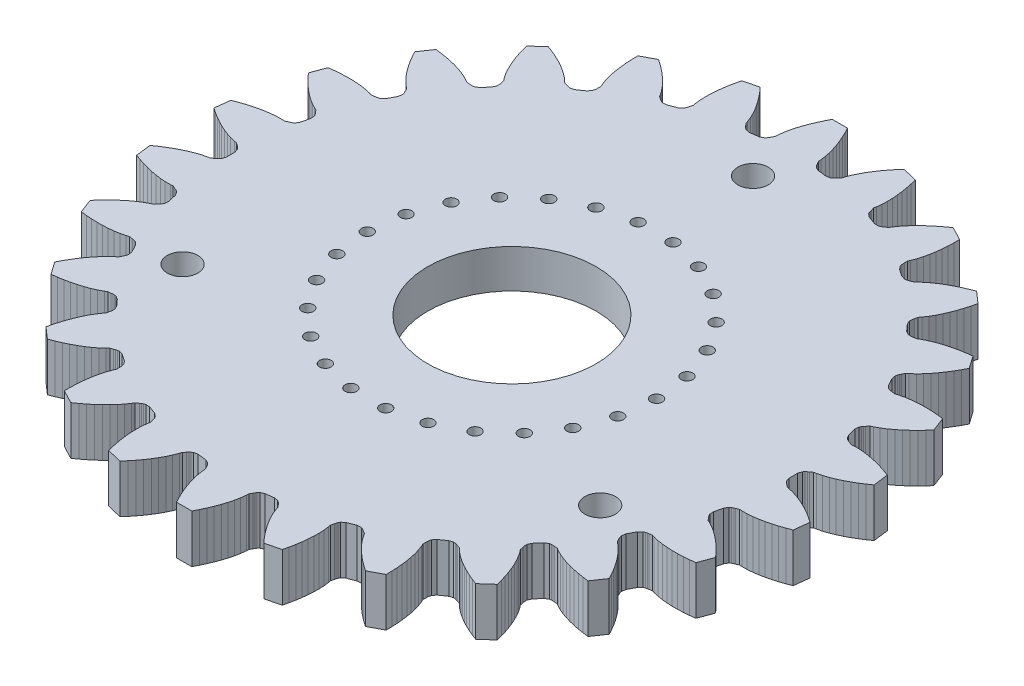
SolidWorks part; units mm, degrees
material "1060 Alloy"
ref_plane "Front Plane" through (0, 0, 0) normal (0, 0, 1) x (1, 0, 0)
ref_plane "Top Plane" through (0, 0, 0) normal (0, 1, 0) x (1, 0, 0)
ref_plane "Right Plane" through (0, 0, 0) normal (1, 0, 0) x (0, 0, -1)
sketch "Sketch1" plane through (0, 0, 0) normal (0, 1, 0) x (1, 0, 0)
  line L0 (0, 0) -> (54.8903, 0) construction
  line L1 (0, 0) -> (47.5263, 11.7142) construction
  line L2 (0, 0) -> (29.6137, 7.2991)
  line L3 (0, 0) -> (32, 0)
  circle A0 centre (0, 0) radius 32 construction
  circle A1 centre (0, 0) radius 30.5 construction
  arc A2 (29.6137, 7.2991) -> (32, 0) centre (21.3514, 0.5583) cw
  circle A3 centre (0, 0) radius 31.25 construction
  dimension "D1" = 62.5
  dimension "D2" = 1.5
  dimension "D4" = 0.75
  dimension "D3" = 13.846
extrude "Extrude ratchet edge" add sketch "Sketch1" along normal blind 10
pattern_circular "Pattern edge to form gear" count 26 over 360 about axis through (0, 10, 0) along (0, -1, 0) of "Extrude ratchet edge" reverse direction yes
sketch "Sketch7" plane through (0, 10, 0) normal (0, 1, 0) x (1, 0, 0)
  circle A0 centre (0, 0) radius 8.7313
  dimension "D1" = 17.4625
sketch "Sketch12" plane through (0, 0, 0) normal (0, -1, 0) x (1, 0, 0)
  line L0 (29.0003, -0.6166) -> (29.1196, -1.0003)
  line L1 (29.1196, -1.0003) -> (29.244, -1.1506)
  line L2 (29.244, -1.1506) -> (29.3694, -1.2597)
  line L3 (29.3694, -1.2597) -> (29.4955, -1.346)
  line L4 (29.4955, -1.346) -> (29.7463, -1.5351)
  line L5 (29.7463, -1.5351) -> (30.0039, -1.5796)
  line L6 (30.0039, -1.5796) -> (30.5166, -1.7122)
  line L7 (30.5166, -1.7122) -> (31.0266, -1.8861)
  line L8 (31.0266, -1.8861) -> (31.5336, -2.0936)
  line L9 (31.5336, -2.0936) -> (32.0376, -2.3308)
  line L10 (32.0376, -2.3308) -> (32.5381, -2.595)
  line L11 (32.5381, -2.595) -> (33.035, -2.8848)
  line L12 (33.035, -2.8848) -> (33.5277, -3.1987)
  line L13 (33.5277, -3.1987) -> (34.0159, -3.5359)
  line L14 (34.0159, -3.5359) -> (33.8164, -5.1042)
  line L15 (33.8164, -5.1042) -> (33.2594, -5.3084)
  line L16 (33.2594, -5.3084) -> (32.7038, -5.4891)
  line L17 (32.7038, -5.4891) -> (32.1503, -5.6453)
  line L18 (32.1503, -5.6453) -> (31.5995, -5.7759)
  line L19 (31.5995, -5.7759) -> (31.0523, -5.8793)
  line L20 (31.0523, -5.8793) -> (30.5094, -5.9534)
  line L21 (30.5094, -5.9534) -> (29.9722, -5.9942)
  line L22 (29.9722, -5.9942) -> (29.4426, -5.9942)
  line L23 (29.4426, -5.9942) -> (29.182, -5.9728)
  line L24 (29.182, -5.9728) -> (28.8919, -6.0931)
  line L25 (28.8919, -6.0931) -> (28.7482, -6.1452)
  line L26 (28.7482, -6.1452) -> (28.5995, -6.2194)
  line L27 (28.5995, -6.2194) -> (28.4414, -6.3338)
  line L28 (28.4414, -6.3338) -> (28.2299, -6.6755)
  line L29 (28.2299, -6.6755) -> (28.0119, -7.539)
  line L30 (28.0119, -7.539) -> (28.0359, -7.9401)
  line L31 (28.0359, -7.9401) -> (28.1207, -8.1159)
  line L32 (28.1207, -8.1159) -> (28.2164, -8.2517)
  line L33 (28.2164, -8.2517) -> (28.3182, -8.3658)
  line L34 (28.3182, -8.3658) -> (28.5164, -8.6094)
  line L35 (28.5164, -8.6094) -> (28.7559, -8.7142)
  line L36 (28.7559, -8.7142) -> (29.222, -8.9657)
  line L37 (29.222, -8.9657) -> (29.6755, -9.2566)
  line L38 (29.6755, -9.2566) -> (30.1181, -9.5794)
  line L39 (30.1181, -9.5794) -> (30.5507, -9.9303)
  line L40 (30.5507, -9.9303) -> (30.9735, -10.3067)
  line L41 (30.9735, -10.3067) -> (31.3865, -10.7069)
  line L42 (31.3865, -10.7069) -> (31.7898, -11.1296)
  line L43 (31.7898, -11.1296) -> (32.1831, -11.5738)
  line L44 (32.1831, -11.5738) -> (31.6141, -13.0488)
  line L45 (31.6141, -13.0488) -> (31.0244, -13.1138)
  line L46 (31.0244, -13.1138) -> (30.4418, -13.1563)
  line L47 (30.4418, -13.1563) -> (29.8669, -13.1754)
  line L48 (29.8669, -13.1754) -> (29.3009, -13.1704)
  line L49 (29.3009, -13.1704) -> (28.7448, -13.1399)
  line L50 (28.7448, -13.1399) -> (28.2, -13.0819)
  line L51 (28.2, -13.0819) -> (27.6686, -12.9929)
  line L52 (27.6686, -12.9929) -> (27.1544, -12.8663)
  line L53 (27.1544, -12.8663) -> (26.9065, -12.7831)
  line L54 (26.9065, -12.7831) -> (26.5961, -12.8305)
  line L55 (26.5961, -12.8305) -> (26.4441, -12.8467)
  line L56 (26.4441, -12.8467) -> (26.2819, -12.8831)
  line L57 (26.2819, -12.8831) -> (26.1011, -12.9564)
  line L58 (26.1011, -12.9564) -> (25.814, -13.2375)
  line L59 (25.814, -13.2375) -> (25.3956, -14.0238)
  line L60 (25.3956, -14.0238) -> (25.3229, -14.4189)
  line L61 (25.3229, -14.4189) -> (25.3632, -14.6099)
  line L62 (25.3632, -14.6099) -> (25.4236, -14.7647)
  line L63 (25.4236, -14.7647) -> (25.4951, -14.8998)
  line L64 (25.4951, -14.8998) -> (25.6292, -15.1838)
  line L65 (25.6292, -15.1838) -> (25.8367, -15.3428)
  line L66 (25.8367, -15.3428) -> (26.2291, -15.6985)
  line L67 (26.2291, -15.6985) -> (26.5998, -16.0895)
  line L68 (26.5998, -16.0895) -> (26.9523, -16.5089)
  line L69 (26.9523, -16.5089) -> (27.2883, -16.9531)
  line L70 (27.2883, -16.9531) -> (27.6087, -17.4197)
  line L71 (27.6087, -17.4197) -> (27.914, -17.9072)
  line L72 (27.914, -17.9072) -> (28.2044, -18.4141)
  line L73 (28.2044, -18.4141) -> (28.48, -18.9395)
  line L74 (28.48, -18.9395) -> (27.5746, -20.2355)
  line L75 (27.5746, -20.2355) -> (26.9864, -20.1575)
  line L76 (26.9864, -20.1575) -> (26.4105, -20.0593)
  line L77 (26.4105, -20.0593) -> (25.8478, -19.9403)
  line L78 (25.8478, -19.9403) -> (25.2994, -19.8)
  line L79 (25.2994, -19.8) -> (24.7668, -19.6373)
  line L80 (24.7668, -19.6373) -> (24.2517, -19.4506)
  line L81 (24.2517, -19.4506) -> (23.7571, -19.237)
  line L82 (23.7571, -19.237) -> (23.2881, -18.991)
  line L83 (23.2881, -18.991) -> (23.0673, -18.8509)
  line L84 (23.0673, -18.8509) -> (22.7546, -18.8226)
  line L85 (22.7546, -18.8226) -> (22.6031, -18.802)
  line L86 (22.6031, -18.802) -> (22.4369, -18.7985)
  line L87 (22.4369, -18.7985) -> (22.2438, -18.8264)
  line L88 (22.2438, -18.8264) -> (21.8978, -19.0306)
  line L89 (21.8978, -19.0306) -> (21.3034, -19.694)
  line L90 (21.3034, -19.694) -> (21.1383, -20.0602)
  line L91 (21.1383, -20.0602) -> (21.1316, -20.2553)
  line L92 (21.1316, -20.2553) -> (21.1532, -20.4201)
  line L93 (21.1532, -20.4201) -> (21.1903, -20.5684)
  line L94 (21.1903, -20.5684) -> (21.2526, -20.8761)
  line L95 (21.2526, -20.8761) -> (21.416, -21.0803)
  line L96 (21.416, -21.0803) -> (21.7119, -21.5195)
  line L97 (21.7119, -21.5195) -> (21.9782, -21.9879)
  line L98 (21.9782, -21.9879) -> (22.2201, -22.4794)
  line L99 (22.2201, -22.4794) -> (22.4401, -22.9911)
  line L100 (22.4401, -22.9911) -> (22.6395, -23.5209)
  line L101 (22.6395, -23.5209) -> (22.8193, -24.0672)
  line L102 (22.8193, -24.0672) -> (22.9799, -24.6289)
  line L103 (22.9799, -24.6289) -> (23.1217, -25.205)
  line L104 (23.1217, -25.205) -> (21.9325, -26.2467)
  line L105 (21.9325, -26.2467) -> (21.3801, -26.0302)
  line L106 (21.3801, -26.0302) -> (20.8445, -25.797)
  line L107 (20.8445, -25.797) -> (20.3266, -25.5468)
  line L108 (20.3266, -25.5468) -> (19.8277, -25.2793)
  line L109 (19.8277, -25.2793) -> (19.3494, -24.9939)
  line L110 (19.3494, -24.9939) -> (18.894, -24.6893)
  line L111 (18.894, -24.6893) -> (18.4649, -24.3636)
  line L112 (18.4649, -24.3636) -> (18.0684, -24.0125)
  line L113 (18.0684, -24.0125) -> (17.8876, -23.8237)
  line L114 (17.8876, -23.8237) -> (17.5907, -23.7213)
  line L115 (17.5907, -23.7213) -> (17.4485, -23.665)
  line L116 (17.4485, -23.665) -> (17.288, -23.6219)
  line L117 (17.288, -23.6219) -> (17.0938, -23.6028)
  line L118 (17.0938, -23.6028) -> (16.709, -23.7182)
  line L119 (16.709, -23.7182) -> (15.9732, -24.22)
  line L120 (15.9732, -24.22) -> (15.7251, -24.5362)
  line L121 (15.7251, -24.5362) -> (15.672, -24.7239)
  line L122 (15.672, -24.7239) -> (15.6536, -24.8891)
  line L123 (15.6536, -24.8891) -> (15.6541, -25.042)
  line L124 (15.6541, -25.042) -> (15.641, -25.3558)
  line L125 (15.641, -25.3558) -> (15.7507, -25.593)
  line L126 (15.7507, -25.593) -> (15.9329, -26.0903)
  line L127 (15.9329, -26.0903) -> (16.0794, -26.6088)
  line L128 (16.0794, -26.6088) -> (16.1966, -27.144)
  line L129 (16.1966, -27.144) -> (16.2878, -27.6934)
  line L130 (16.2878, -27.6934) -> (16.3546, -28.2555)
  line L131 (16.3546, -28.2555) -> (16.3984, -28.829)
  line L132 (16.3984, -28.829) -> (16.4199, -29.4128)
  line L133 (16.4199, -29.4128) -> (16.4198, -30.0061)
  line L134 (16.4198, -30.0061) -> (15.0158, -30.7329)
  line L135 (15.0158, -30.7329) -> (14.5313, -30.3905)
  line L136 (14.5313, -30.3905) -> (14.067, -30.0359)
  line L137 (14.067, -30.0359) -> (13.624, -29.6691)
  line L138 (13.624, -29.6691) -> (13.2037, -29.29)
  line L139 (13.2037, -29.29) -> (12.8076, -28.8984)
  line L140 (12.8076, -28.8984) -> (12.4383, -28.4937)
  line L141 (12.4383, -28.4937) -> (12.0996, -28.0747)
  line L142 (12.0996, -28.0747) -> (11.7986, -27.6389)
  line L143 (11.7986, -27.6389) -> (11.6683, -27.4123)
  line L144 (11.6683, -27.4123) -> (11.4045, -27.2419)
  line L145 (11.4045, -27.2419) -> (11.28, -27.1532)
  line L146 (11.28, -27.1532) -> (11.1345, -27.0729)
  line L147 (11.1345, -27.0729) -> (10.9505, -27.0079)
  line L148 (10.9505, -27.0079) -> (10.5492, -27.0279)
  line L149 (10.5492, -27.0279) -> (9.7146, -27.339)
  line L150 (9.7146, -27.339) -> (9.3982, -27.5866)
  line L151 (9.3982, -27.5866) -> (9.3017, -27.7562)
  line L152 (9.3017, -27.7562) -> (9.2442, -27.9122)
  line L153 (9.2442, -27.9122) -> (9.2082, -28.0607)
  line L154 (9.2082, -28.0607) -> (9.1203, -28.3622)
  line L155 (9.1203, -28.3622) -> (9.1701, -28.6189)
  line L156 (9.1701, -28.6189) -> (9.2279, -29.1453)
  line L157 (9.2279, -29.1453) -> (9.2461, -29.6838)
  line L158 (9.2461, -29.6838) -> (9.2319, -30.2315)
  line L159 (9.2319, -30.2315) -> (9.1888, -30.7868)
  line L160 (9.1888, -30.7868) -> (9.1192, -31.3485)
  line L161 (9.1192, -31.3485) -> (9.0245, -31.9158)
  line L162 (9.0245, -31.9158) -> (8.9057, -32.4878)
  line L163 (8.9057, -32.4878) -> (8.7636, -33.0638)
  line L164 (8.7636, -33.0638) -> (7.2264, -33.4335)
  line L165 (7.2264, -33.4335) -> (6.8379, -32.9851)
  line L166 (6.8379, -32.9851) -> (6.472, -32.5297)
  line L167 (6.472, -32.5297) -> (6.1297, -32.0675)
  line L168 (6.1297, -32.0675) -> (5.8123, -31.5988)
  line L169 (5.8123, -31.5988) -> (5.5215, -31.1238)
  line L170 (5.5215, -31.1238) -> (5.2598, -30.6425)
  line L171 (5.2598, -30.6425) -> (5.0311, -30.1547)
  line L172 (5.0311, -30.1547) -> (4.8432, -29.6595)
  line L173 (4.8432, -29.6595) -> (4.7709, -29.4083)
  line L174 (4.7709, -29.4083) -> (4.5555, -29.1797)
  line L175 (4.5555, -29.1797) -> (4.4559, -29.0638)
  line L176 (4.4559, -29.0638) -> (4.3338, -28.951)
  line L177 (4.3338, -28.951) -> (4.1707, -28.8438)
  line L178 (4.1707, -28.8438) -> (3.7763, -28.7672)
  line L179 (3.7763, -28.7672) -> (2.8915, -28.8696)
  line L180 (2.8915, -28.8696) -> (2.525, -29.0342)
  line L181 (2.525, -29.0342) -> (2.3907, -29.1758)
  line L182 (2.3907, -29.1758) -> (2.2976, -29.3135)
  line L183 (2.2976, -29.3135) -> (2.2271, -29.4491)
  line L184 (2.2271, -29.4491) -> (2.0696, -29.7208)
  line L185 (2.0696, -29.7208) -> (2.0565, -29.9819)
  line L186 (2.0565, -29.9819) -> (1.9867, -30.5069)
  line L187 (1.9867, -30.5069) -> (1.8755, -31.0341)
  line L188 (1.8755, -31.0341) -> (1.7306, -31.5624)
  line L189 (1.7306, -31.5624) -> (1.5559, -32.0913)
  line L190 (1.5559, -32.0913) -> (1.3539, -32.6201)
  line L191 (1.3539, -32.6201) -> (1.1262, -33.1482)
  line L192 (1.1262, -33.1482) -> (0.8739, -33.6752)
  line L193 (0.8739, -33.6752) -> (0.5981, -34.2004)
  line L194 (0.5981, -34.2004) -> (-0.9829, -34.1915)
  line L195 (-0.9829, -34.1915) -> (-1.2528, -33.6632)
  line L196 (-1.2528, -33.6632) -> (-1.499, -33.1334)
  line L197 (-1.499, -33.1334) -> (-1.7208, -32.6027)
  line L198 (-1.7208, -32.6027) -> (-1.9169, -32.0717)
  line L199 (-1.9169, -32.0717) -> (-2.0855, -31.5409)
  line L200 (-2.0855, -31.5409) -> (-2.2244, -31.011)
  line L201 (-2.2244, -31.011) -> (-2.3297, -30.4826)
  line L202 (-2.3297, -30.4826) -> (-2.3936, -29.9568)
  line L203 (-2.3936, -29.9568) -> (-2.4037, -29.6956)
  line L204 (-2.4037, -29.6956) -> (-2.5581, -29.4221)
  line L205 (-2.5581, -29.4221) -> (-2.6272, -29.2857)
  line L206 (-2.6272, -29.2857) -> (-2.7187, -29.147)
  line L207 (-2.7187, -29.147) -> (-2.8514, -29.0039)
  line L208 (-2.8514, -29.0039) -> (-3.216, -28.8351)
  line L209 (-3.216, -28.8351) -> (-4.0996, -28.7228)
  line L210 (-4.0996, -28.7228) -> (-4.4948, -28.7949)
  line L211 (-4.4948, -28.7949) -> (-4.6591, -28.9003)
  line L212 (-4.6591, -28.9003) -> (-4.7824, -29.0117)
  line L213 (-4.7824, -29.0117) -> (-4.8834, -29.1265)
  line L214 (-4.8834, -29.1265) -> (-5.1013, -29.3526)
  line L215 (-5.1013, -29.3526) -> (-5.1765, -29.603)
  line L216 (-5.1765, -29.603) -> (-5.37, -30.096)
  line L217 (-5.37, -30.096) -> (-5.6041, -30.5812)
  line L218 (-5.6041, -30.5812) -> (-5.8712, -31.0596)
  line L219 (-5.8712, -31.0596) -> (-6.1674, -31.5313)
  line L220 (-6.1674, -31.5313) -> (-6.4901, -31.9963)
  line L221 (-6.4901, -31.9963) -> (-6.8376, -32.4546)
  line L222 (-6.8376, -32.4546) -> (-7.2086, -32.9059)
  line L223 (-7.2086, -32.9059) -> (-7.6021, -33.3499)
  line L224 (-7.6021, -33.3499) -> (-9.135, -32.9629)
  line L225 (-9.135, -32.9629) -> (-9.2706, -32.3853)
  line L226 (-9.2706, -32.3853) -> (-9.383, -31.812)
  line L227 (-9.383, -31.812) -> (-9.4713, -31.2437)
  line L228 (-9.4713, -31.2437) -> (-9.5346, -30.6812)
  line L229 (-9.5346, -30.6812) -> (-9.5713, -30.1254)
  line L230 (-9.5713, -30.1254) -> (-9.5793, -29.5776)
  line L231 (-9.5793, -29.5776) -> (-9.5551, -29.0394)
  line L232 (-9.5551, -29.0394) -> (-9.4913, -28.5136)
  line L233 (-9.4913, -28.5136) -> (-9.4387, -28.2576)
  line L234 (-9.4387, -28.2576) -> (-9.5231, -27.9551)
  line L235 (-9.5231, -27.9551) -> (-9.5575, -27.8061)
  line L236 (-9.5575, -27.8061) -> (-9.6132, -27.6496)
  line L237 (-9.6132, -27.6496) -> (-9.7078, -27.4789)
  line L238 (-9.7078, -27.4789) -> (-10.0214, -27.2277)
  line L239 (-10.0214, -27.2277) -> (-10.8524, -26.9072)
  line L240 (-10.8524, -26.9072) -> (-11.2535, -26.8827)
  line L241 (-11.2535, -26.8827) -> (-11.4382, -26.9456)
  line L242 (-11.4382, -26.9456) -> (-11.5846, -27.0243)
  line L243 (-11.5846, -27.0243) -> (-11.7101, -27.1116)
  line L244 (-11.7101, -27.1116) -> (-11.9758, -27.279)
  line L245 (-11.9758, -27.279) -> (-12.1087, -27.5041)
  line L246 (-12.1087, -27.5041) -> (-12.4145, -27.9365)
  line L247 (-12.4145, -27.9365) -> (-12.758, -28.3516)
  line L248 (-12.758, -28.3516) -> (-13.1318, -28.7521)
  line L249 (-13.1318, -28.7521) -> (-13.5322, -29.1392)
  line L250 (-13.5322, -29.1392) -> (-13.9568, -29.5135)
  line L251 (-13.9568, -29.5135) -> (-14.4039, -29.8753)
  line L252 (-14.4039, -29.8753) -> (-14.8722, -30.2247)
  line L253 (-14.8722, -30.2247) -> (-15.3605, -30.5616)
  line L254 (-15.3605, -30.5616) -> (-16.7562, -29.819)
  line L255 (-16.7562, -29.819) -> (-16.7497, -29.2258)
  line L256 (-16.7497, -29.2258) -> (-16.7216, -28.6422)
  line L257 (-16.7216, -28.6422) -> (-16.6713, -28.0693)
  line L258 (-16.6713, -28.0693) -> (-16.5981, -27.508)
  line L259 (-16.5981, -27.508) -> (-16.5008, -26.9596)
  line L260 (-16.5008, -26.9596) -> (-16.3775, -26.4258)
  line L261 (-16.3775, -26.4258) -> (-16.2252, -25.909)
  line L262 (-16.2252, -25.909) -> (-16.0374, -25.4138)
  line L263 (-16.0374, -25.4138) -> (-15.925, -25.1778)
  line L264 (-15.925, -25.1778) -> (-15.9346, -24.8639)
  line L265 (-15.9346, -24.8639) -> (-15.9324, -24.711)
  line L266 (-15.9324, -24.711) -> (-15.949, -24.5456)
  line L267 (-15.949, -24.5456) -> (-15.9999, -24.3573)
  line L268 (-15.9999, -24.3573) -> (-16.2444, -24.0384)
  line L269 (-16.2444, -24.0384) -> (-16.9745, -23.5283)
  line L270 (-16.9745, -23.5283) -> (-17.358, -23.4085)
  line L271 (-17.358, -23.4085) -> (-17.5524, -23.4254)
  line L272 (-17.5524, -23.4254) -> (-17.7134, -23.4668)
  line L273 (-17.7134, -23.4668) -> (-17.8562, -23.5215)
  line L274 (-17.8562, -23.5215) -> (-18.1542, -23.6204)
  line L275 (-18.1542, -23.6204) -> (-18.3371, -23.8072)
  line L276 (-18.3371, -23.8072) -> (-18.7375, -24.1538)
  line L277 (-18.7375, -24.1538) -> (-19.1704, -24.4747)
  line L278 (-19.1704, -24.4747) -> (-19.6292, -24.7741)
  line L279 (-19.6292, -24.7741) -> (-20.1106, -25.0541)
  line L280 (-20.1106, -25.0541) -> (-20.6125, -25.316)
  line L281 (-20.6125, -25.316) -> (-21.1332, -25.5603)
  line L282 (-21.1332, -25.5603) -> (-21.6714, -25.7874)
  line L283 (-21.6714, -25.7874) -> (-22.2262, -25.9977)
  line L284 (-22.2262, -25.9977) -> (-23.4036, -24.9426)
  line L285 (-23.4036, -24.9426) -> (-23.2553, -24.3682)
  line L286 (-23.2553, -24.3682) -> (-23.0883, -23.8083)
  line L287 (-23.0883, -23.8083) -> (-22.9024, -23.2641)
  line L288 (-22.9024, -23.2641) -> (-22.6971, -22.7366)
  line L289 (-22.6971, -22.7366) -> (-22.4713, -22.2274)
  line L290 (-22.4713, -22.2274) -> (-22.2239, -21.7386)
  line L291 (-22.2239, -21.7386) -> (-21.9523, -21.2733)
  line L292 (-21.9523, -21.2733) -> (-21.6515, -20.8374)
  line L293 (-21.6515, -20.8374) -> (-21.4858, -20.6352)
  line L294 (-21.4858, -20.6352) -> (-21.4201, -20.3281)
  line L295 (-21.4201, -20.3281) -> (-21.3813, -20.1802)
  line L296 (-21.3813, -20.1802) -> (-21.3578, -20.0157)
  line L297 (-21.3578, -20.0157) -> (-21.3622, -19.8206)
  line L298 (-21.3622, -19.8206) -> (-21.5232, -19.4525)
  line L299 (-21.5232, -19.4525) -> (-22.1101, -18.7825)
  line L300 (-22.1101, -18.7825) -> (-22.4538, -18.5744)
  line L301 (-22.4538, -18.5744) -> (-22.6466, -18.5443)
  line L302 (-22.6466, -18.5443) -> (-22.8128, -18.5459)
  line L303 (-22.8128, -18.5459) -> (-22.9645, -18.5648)
  line L304 (-22.9645, -18.5648) -> (-23.2775, -18.5896)
  line L305 (-23.2775, -18.5896) -> (-23.4999, -18.7272)
  line L306 (-23.4999, -18.7272) -> (-23.9716, -18.9679)
  line L307 (-23.9716, -18.9679) -> (-24.4686, -19.1758)
  line L308 (-24.4686, -19.1758) -> (-24.9858, -19.3568)
  line L309 (-24.9858, -19.3568) -> (-25.5202, -19.5135)
  line L310 (-25.5202, -19.5135) -> (-26.0702, -19.6476)
  line L311 (-26.0702, -19.6476) -> (-26.6342, -19.7602)
  line L312 (-26.6342, -19.7602) -> (-27.2111, -19.8519)
  line L313 (-27.2111, -19.8519) -> (-27.8001, -19.9233)
  line L314 (-27.8001, -19.9233) -> (-28.6909, -18.6171)
  line L315 (-28.6909, -18.6171) -> (-28.4094, -18.0949)
  line L316 (-28.4094, -18.0949) -> (-28.1133, -17.5912)
  line L317 (-28.1133, -17.5912) -> (-27.8025, -17.1073)
  line L318 (-27.8025, -17.1073) -> (-27.4769, -16.6443)
  line L319 (-27.4769, -16.6443) -> (-27.1359, -16.2039)
  line L320 (-27.1359, -16.2039) -> (-26.7786, -15.7885)
  line L321 (-26.7786, -15.7885) -> (-26.4036, -15.4018)
  line L322 (-26.4036, -15.4018) -> (-26.0072, -15.0505)
  line L323 (-26.0072, -15.0505) -> (-25.7979, -14.8938)
  line L324 (-25.7979, -14.8938) -> (-25.6606, -14.6114)
  line L325 (-25.6606, -14.6114) -> (-25.5876, -14.4771)
  line L326 (-25.5876, -14.4771) -> (-25.5254, -14.3229)
  line L327 (-25.5254, -14.3229) -> (-25.483, -14.1325)
  line L328 (-25.483, -14.1325) -> (-25.5512, -13.7365)
  line L329 (-25.5512, -13.7365) -> (-25.9607, -12.9455)
  line L330 (-25.9607, -12.9455) -> (-26.2446, -12.6612)
  line L331 (-26.2446, -12.6612) -> (-26.4246, -12.5859)
  line L332 (-26.4246, -12.5859) -> (-26.5864, -12.5476)
  line L333 (-26.5864, -12.5476) -> (-26.7382, -12.5297)
  line L334 (-26.7382, -12.5297) -> (-27.0481, -12.4789)
  line L335 (-27.0481, -12.4789) -> (-27.2968, -12.5592)
  line L336 (-27.2968, -12.5592) -> (-27.8125, -12.6801)
  line L337 (-27.8125, -12.6801) -> (-28.3448, -12.763)
  line L338 (-28.3448, -12.763) -> (-28.8902, -12.8149)
  line L339 (-28.8902, -12.8149) -> (-29.4467, -12.8392)
  line L340 (-29.4467, -12.8392) -> (-30.0127, -12.8378)
  line L341 (-30.0127, -12.8378) -> (-30.5873, -12.8121)
  line L342 (-30.5873, -12.8121) -> (-31.1694, -12.7631)
  line L343 (-31.1694, -12.7631) -> (-31.7584, -12.6915)
  line L344 (-31.7584, -12.6915) -> (-32.3107, -11.2101)
  line L345 (-32.3107, -11.2101) -> (-31.9124, -10.7704)
  line L346 (-31.9124, -10.7704) -> (-31.5044, -10.3522)
  line L347 (-31.5044, -10.3522) -> (-31.0868, -9.9567)
  line L348 (-31.0868, -9.9567) -> (-30.6598, -9.5851)
  line L349 (-30.6598, -9.5851) -> (-30.2233, -9.2392)
  line L350 (-30.2233, -9.2392) -> (-29.7771, -8.9214)
  line L351 (-29.7771, -8.9214) -> (-29.3203, -8.6356)
  line L352 (-29.3203, -8.6356) -> (-28.8514, -8.3894)
  line L353 (-28.8514, -8.3894) -> (-28.6108, -8.2873)
  line L354 (-28.6108, -8.2873) -> (-28.4098, -8.0459)
  line L355 (-28.4098, -8.0459) -> (-28.3068, -7.933)
  line L356 (-28.3068, -7.933) -> (-28.2095, -7.7982)
  line L357 (-28.2095, -7.7982) -> (-28.1228, -7.6234)
  line L358 (-28.1228, -7.6234) -> (-28.0943, -7.2226)
  line L359 (-28.0943, -7.2226) -> (-28.3025, -6.3567)
  line L360 (-28.3025, -6.3567) -> (-28.5102, -6.0127)
  line L361 (-28.5102, -6.0127) -> (-28.6669, -5.8964)
  line L362 (-28.6669, -5.8964) -> (-28.8148, -5.8206)
  line L363 (-28.8148, -5.8206) -> (-28.9579, -5.7669)
  line L364 (-28.9579, -5.7669) -> (-29.2466, -5.6433)
  line L365 (-29.2466, -5.6433) -> (-29.5074, -5.6618)
  line L366 (-29.5074, -5.6618) -> (-30.037, -5.6558)
  line L367 (-30.037, -5.6558) -> (-30.5737, -5.6089)
  line L368 (-30.5737, -5.6089) -> (-31.1157, -5.5288)
  line L369 (-31.1157, -5.5288) -> (-31.6618, -5.4192)
  line L370 (-31.6618, -5.4192) -> (-32.211, -5.2824)
  line L371 (-32.211, -5.2824) -> (-32.7628, -5.1199)
  line L372 (-32.7628, -5.1199) -> (-33.3163, -4.933)
  line L373 (-33.3163, -4.933) -> (-33.871, -4.7225)
  line L374 (-33.871, -4.7225) -> (-34.0527, -3.152)
  line L375 (-34.0527, -3.152) -> (-33.5607, -2.8204)
  line L376 (-33.5607, -2.8204) -> (-33.0645, -2.5121)
  line L377 (-33.0645, -2.5121) -> (-32.5644, -2.228)
  line L378 (-32.5644, -2.228) -> (-32.0609, -1.9693)
  line L379 (-32.0609, -1.9693) -> (-31.5543, -1.7379)
  line L380 (-31.5543, -1.7379) -> (-31.045, -1.5361)
  line L381 (-31.045, -1.5361) -> (-30.5331, -1.3679)
  line L382 (-30.5331, -1.3679) -> (-30.0189, -1.2411)
  line L383 (-30.0189, -1.2411) -> (-29.7608, -1.1996)
  line L384 (-29.7608, -1.1996) -> (-29.5079, -1.0133)
  line L385 (-29.5079, -1.0133) -> (-29.3809, -0.9284)
  line L386 (-29.3809, -0.9284) -> (-29.2542, -0.8208)
  line L387 (-29.2542, -0.8208) -> (-29.1281, -0.6718)
  line L388 (-29.1281, -0.6718) -> (-29.0045, -0.2895)
  line L389 (-29.0045, -0.2895) -> (-28.9995, 0.6011)
  line L390 (-28.9995, 0.6011) -> (-29.1188, 0.9848)
  line L391 (-29.1188, 0.9848) -> (-29.2432, 1.1352)
  line L392 (-29.2432, 1.1352) -> (-29.3686, 1.2442)
  line L393 (-29.3686, 1.2442) -> (-29.4947, 1.3306)
  line L394 (-29.4947, 1.3306) -> (-29.7455, 1.5197)
  line L395 (-29.7455, 1.5197) -> (-30.0031, 1.5641)
  line L396 (-30.0031, 1.5641) -> (-30.5158, 1.6968)
  line L397 (-30.5158, 1.6968) -> (-31.0257, 1.8707)
  line L398 (-31.0257, 1.8707) -> (-31.5328, 2.0782)
  line L399 (-31.5328, 2.0782) -> (-32.0368, 2.3153)
  line L400 (-32.0368, 2.3153) -> (-32.5373, 2.5796)
  line L401 (-32.5373, 2.5796) -> (-33.0342, 2.8694)
  line L402 (-33.0342, 2.8694) -> (-33.5269, 3.1833)
  line L403 (-33.5269, 3.1833) -> (-34.0151, 3.5204)
  line L404 (-34.0151, 3.5204) -> (-33.8156, 5.0888)
  line L405 (-33.8156, 5.0888) -> (-33.2586, 5.293)
  line L406 (-33.2586, 5.293) -> (-32.703, 5.4737)
  line L407 (-32.703, 5.4737) -> (-32.1495, 5.6298)
  line L408 (-32.1495, 5.6298) -> (-31.5987, 5.7604)
  line L409 (-31.5987, 5.7604) -> (-31.0515, 5.8639)
  line L410 (-31.0515, 5.8639) -> (-30.5086, 5.9379)
  line L411 (-30.5086, 5.9379) -> (-29.9714, 5.9787)
  line L412 (-29.9714, 5.9787) -> (-29.4418, 5.9788)
  line L413 (-29.4418, 5.9788) -> (-29.1812, 5.9574)
  line L414 (-29.1812, 5.9574) -> (-28.8911, 6.0777)
  line L415 (-28.8911, 6.0777) -> (-28.7474, 6.1298)
  line L416 (-28.7474, 6.1298) -> (-28.5987, 6.2039)
  line L417 (-28.5987, 6.2039) -> (-28.4406, 6.3184)
  line L418 (-28.4406, 6.3184) -> (-28.2291, 6.66)
  line L419 (-28.2291, 6.66) -> (-28.0111, 7.5236)
  line L420 (-28.0111, 7.5236) -> (-28.0351, 7.9247)
  line L421 (-28.0351, 7.9247) -> (-28.1199, 8.1004)
  line L422 (-28.1199, 8.1004) -> (-28.2156, 8.2363)
  line L423 (-28.2156, 8.2363) -> (-28.3174, 8.3504)
  line L424 (-28.3174, 8.3504) -> (-28.5156, 8.594)
  line L425 (-28.5156, 8.594) -> (-28.7551, 8.6988)
  line L426 (-28.7551, 8.6988) -> (-29.2212, 8.9502)
  line L427 (-29.2212, 8.9502) -> (-29.6746, 9.2412)
  line L428 (-29.6746, 9.2412) -> (-30.1173, 9.564)
  line L429 (-30.1173, 9.564) -> (-30.5499, 9.9148)
  line L430 (-30.5499, 9.9148) -> (-30.9727, 10.2912)
  line L431 (-30.9727, 10.2912) -> (-31.3857, 10.6914)
  line L432 (-31.3857, 10.6914) -> (-31.789, 11.1142)
  line L433 (-31.789, 11.1142) -> (-32.1823, 11.5583)
  line L434 (-32.1823, 11.5583) -> (-31.6133, 13.0334)
  line L435 (-31.6133, 13.0334) -> (-31.0236, 13.0984)
  line L436 (-31.0236, 13.0984) -> (-30.4409, 13.1408)
  line L437 (-30.4409, 13.1408) -> (-29.8661, 13.16)
  line L438 (-29.8661, 13.16) -> (-29.3001, 13.155)
  line L439 (-29.3001, 13.155) -> (-28.744, 13.1245)
  line L440 (-28.744, 13.1245) -> (-28.1992, 13.0665)
  line L441 (-28.1992, 13.0665) -> (-27.6678, 12.9775)
  line L442 (-27.6678, 12.9775) -> (-27.1536, 12.8508)
  line L443 (-27.1536, 12.8508) -> (-26.9057, 12.7677)
  line L444 (-26.9057, 12.7677) -> (-26.5953, 12.8151)
  line L445 (-26.5953, 12.8151) -> (-26.4433, 12.8312)
  line L446 (-26.4433, 12.8312) -> (-26.2811, 12.8676)
  line L447 (-26.2811, 12.8676) -> (-26.1002, 12.941)
  line L448 (-26.1002, 12.941) -> (-25.8131, 13.222)
  line L449 (-25.8131, 13.222) -> (-25.3948, 14.0083)
  line L450 (-25.3948, 14.0083) -> (-25.3221, 14.4035)
  line L451 (-25.3221, 14.4035) -> (-25.3623, 14.5945)
  line L452 (-25.3623, 14.5945) -> (-25.4228, 14.7493)
  line L453 (-25.4228, 14.7493) -> (-25.4943, 14.8844)
  line L454 (-25.4943, 14.8844) -> (-25.6284, 15.1683)
  line L455 (-25.6284, 15.1683) -> (-25.8359, 15.3274)
  line L456 (-25.8359, 15.3274) -> (-26.2283, 15.6831)
  line L457 (-26.2283, 15.6831) -> (-26.5989, 16.0741)
  line L458 (-26.5989, 16.0741) -> (-26.9515, 16.4935)
  line L459 (-26.9515, 16.4935) -> (-27.2875, 16.9377)
  line L460 (-27.2875, 16.9377) -> (-27.6079, 17.4043)
  line L461 (-27.6079, 17.4043) -> (-27.9132, 17.8917)
  line L462 (-27.9132, 17.8917) -> (-28.2036, 18.3987)
  line L463 (-28.2036, 18.3987) -> (-28.4792, 18.9241)
  line L464 (-28.4792, 18.9241) -> (-27.5738, 20.2201)
  line L465 (-27.5738, 20.2201) -> (-26.9856, 20.1421)
  line L466 (-26.9856, 20.1421) -> (-26.4097, 20.0438)
  line L467 (-26.4097, 20.0438) -> (-25.847, 19.9249)
  line L468 (-25.847, 19.9249) -> (-25.2986, 19.7846)
  line L469 (-25.2986, 19.7846) -> (-24.766, 19.6219)
  line L470 (-24.766, 19.6219) -> (-24.2509, 19.4351)
  line L471 (-24.2509, 19.4351) -> (-23.7562, 19.2216)
  line L472 (-23.7562, 19.2216) -> (-23.2873, 18.9756)
  line L473 (-23.2873, 18.9756) -> (-23.0665, 18.8355)
  line L474 (-23.0665, 18.8355) -> (-22.7538, 18.8072)
  line L475 (-22.7538, 18.8072) -> (-22.6023, 18.7865)
  line L476 (-22.6023, 18.7865) -> (-22.4361, 18.7831)
  line L477 (-22.4361, 18.7831) -> (-22.243, 18.811)
  line L478 (-22.243, 18.811) -> (-21.897, 19.0152)
  line L479 (-21.897, 19.0152) -> (-21.3026, 19.6785)
  line L480 (-21.3026, 19.6785) -> (-21.1374, 20.0448)
  line L481 (-21.1374, 20.0448) -> (-21.1308, 20.2399)
  line L482 (-21.1308, 20.2399) -> (-21.1524, 20.4046)
  line L483 (-21.1524, 20.4046) -> (-21.1895, 20.5529)
  line L484 (-21.1895, 20.5529) -> (-21.2518, 20.8607)
  line L485 (-21.2518, 20.8607) -> (-21.4152, 21.0648)
  line L486 (-21.4152, 21.0648) -> (-21.7111, 21.5041)
  line L487 (-21.7111, 21.5041) -> (-21.9774, 21.9724)
  line L488 (-21.9774, 21.9724) -> (-22.2193, 22.464)
  line L489 (-22.2193, 22.464) -> (-22.4393, 22.9757)
  line L490 (-22.4393, 22.9757) -> (-22.6387, 23.5054)
  line L491 (-22.6387, 23.5054) -> (-22.8185, 24.0518)
  line L492 (-22.8185, 24.0518) -> (-22.9791, 24.6135)
  line L493 (-22.9791, 24.6135) -> (-23.1209, 25.1896)
  line L494 (-23.1209, 25.1896) -> (-21.9317, 26.2312)
  line L495 (-21.9317, 26.2312) -> (-21.3793, 26.0148)
  line L496 (-21.3793, 26.0148) -> (-20.8436, 25.7815)
  line L497 (-20.8436, 25.7815) -> (-20.3258, 25.5314)
  line L498 (-20.3258, 25.5314) -> (-19.8269, 25.2639)
  line L499 (-19.8269, 25.2639) -> (-19.3486, 24.9785)
  line L500 (-19.3486, 24.9785) -> (-18.8932, 24.6739)
  line L501 (-18.8932, 24.6739) -> (-18.464, 24.3482)
  line L502 (-18.464, 24.3482) -> (-18.0676, 23.997)
  line L503 (-18.0676, 23.997) -> (-17.8868, 23.8082)
  line L504 (-17.8868, 23.8082) -> (-17.5899, 23.7059)
  line L505 (-17.5899, 23.7059) -> (-17.4477, 23.6496)
  line L506 (-17.4477, 23.6496) -> (-17.2872, 23.6065)
  line L507 (-17.2872, 23.6065) -> (-17.093, 23.5873)
  line L508 (-17.093, 23.5873) -> (-16.7082, 23.7028)
  line L509 (-16.7082, 23.7028) -> (-15.9723, 24.2046)
  line L510 (-15.9723, 24.2046) -> (-15.7243, 24.5207)
  line L511 (-15.7243, 24.5207) -> (-15.6712, 24.7085)
  line L512 (-15.6712, 24.7085) -> (-15.6528, 24.8737)
  line L513 (-15.6528, 24.8737) -> (-15.6533, 25.0266)
  line L514 (-15.6533, 25.0266) -> (-15.6401, 25.3403)
  line L515 (-15.6401, 25.3403) -> (-15.7499, 25.5776)
  line L516 (-15.7499, 25.5776) -> (-15.932, 26.0749)
  line L517 (-15.932, 26.0749) -> (-16.0786, 26.5934)
  line L518 (-16.0786, 26.5934) -> (-16.1958, 27.1285)
  line L519 (-16.1958, 27.1285) -> (-16.2869, 27.678)
  line L520 (-16.2869, 27.678) -> (-16.3538, 28.2401)
  line L521 (-16.3538, 28.2401) -> (-16.3976, 28.8136)
  line L522 (-16.3976, 28.8136) -> (-16.4191, 29.3974)
  line L523 (-16.4191, 29.3974) -> (-16.419, 29.9907)
  line L524 (-16.419, 29.9907) -> (-15.015, 30.7175)
  line L525 (-15.015, 30.7175) -> (-14.5305, 30.3751)
  line L526 (-14.5305, 30.3751) -> (-14.0662, 30.0205)
  line L527 (-14.0662, 30.0205) -> (-13.6232, 29.6536)
  line L528 (-13.6232, 29.6536) -> (-13.2028, 29.2746)
  line L529 (-13.2028, 29.2746) -> (-12.8068, 28.8829)
  line L530 (-12.8068, 28.8829) -> (-12.4375, 28.4782)
  line L531 (-12.4375, 28.4782) -> (-12.0988, 28.0593)
  line L532 (-12.0988, 28.0593) -> (-11.7978, 27.6235)
  line L533 (-11.7978, 27.6235) -> (-11.6675, 27.3969)
  line L534 (-11.6675, 27.3969) -> (-11.4037, 27.2265)
  line L535 (-11.4037, 27.2265) -> (-11.2792, 27.1378)
  line L536 (-11.2792, 27.1378) -> (-11.1336, 27.0575)
  line L537 (-11.1336, 27.0575) -> (-10.9497, 26.9924)
  line L538 (-10.9497, 26.9924) -> (-10.5484, 27.0125)
  line L539 (-10.5484, 27.0125) -> (-9.7138, 27.3236)
  line L540 (-9.7138, 27.3236) -> (-9.3974, 27.5712)
  line L541 (-9.3974, 27.5712) -> (-9.3009, 27.7408)
  line L542 (-9.3009, 27.7408) -> (-9.2434, 27.8967)
  line L543 (-9.2434, 27.8967) -> (-9.2073, 28.0453)
  line L544 (-9.2073, 28.0453) -> (-9.1195, 28.3468)
  line L545 (-9.1195, 28.3468) -> (-9.1693, 28.6034)
  line L546 (-9.1693, 28.6034) -> (-9.2271, 29.1299)
  line L547 (-9.2271, 29.1299) -> (-9.2453, 29.6683)
  line L548 (-9.2453, 29.6683) -> (-9.231, 30.216)
  line L549 (-9.231, 30.216) -> (-9.188, 30.7713)
  line L550 (-9.188, 30.7713) -> (-9.1184, 31.3331)
  line L551 (-9.1184, 31.3331) -> (-9.0237, 31.9004)
  line L552 (-9.0237, 31.9004) -> (-8.9049, 32.4724)
  line L553 (-8.9049, 32.4724) -> (-8.7628, 33.0484)
  line L554 (-8.7628, 33.0484) -> (-7.2256, 33.4181)
  line L555 (-7.2256, 33.4181) -> (-6.8371, 32.9697)
  line L556 (-6.8371, 32.9697) -> (-6.4712, 32.5142)
  line L557 (-6.4712, 32.5142) -> (-6.1289, 32.0521)
  line L558 (-6.1289, 32.0521) -> (-5.8115, 31.5834)
  line L559 (-5.8115, 31.5834) -> (-5.5207, 31.1084)
  line L560 (-5.5207, 31.1084) -> (-5.259, 30.6271)
  line L561 (-5.259, 30.6271) -> (-5.0303, 30.1392)
  line L562 (-5.0303, 30.1392) -> (-4.8424, 29.644)
  line L563 (-4.8424, 29.644) -> (-4.7701, 29.3928)
  line L564 (-4.7701, 29.3928) -> (-4.5547, 29.1643)
  line L565 (-4.5547, 29.1643) -> (-4.4551, 29.0483)
  line L566 (-4.4551, 29.0483) -> (-4.333, 28.9356)
  line L567 (-4.333, 28.9356) -> (-4.1699, 28.8284)
  line L568 (-4.1699, 28.8284) -> (-3.7755, 28.7518)
  line L569 (-3.7755, 28.7518) -> (-2.8907, 28.8541)
  line L570 (-2.8907, 28.8541) -> (-2.5242, 29.0188)
  line L571 (-2.5242, 29.0188) -> (-2.3899, 29.1604)
  line L572 (-2.3899, 29.1604) -> (-2.2968, 29.2981)
  line L573 (-2.2968, 29.2981) -> (-2.2263, 29.4337)
  line L574 (-2.2263, 29.4337) -> (-2.0688, 29.7054)
  line L575 (-2.0688, 29.7054) -> (-2.0557, 29.9665)
  line L576 (-2.0557, 29.9665) -> (-1.9859, 30.4915)
  line L577 (-1.9859, 30.4915) -> (-1.8747, 31.0186)
  line L578 (-1.8747, 31.0186) -> (-1.7298, 31.547)
  line L579 (-1.7298, 31.547) -> (-1.5551, 32.0759)
  line L580 (-1.5551, 32.0759) -> (-1.3531, 32.6047)
  line L581 (-1.3531, 32.6047) -> (-1.1254, 33.1328)
  line L582 (-1.1254, 33.1328) -> (-0.8731, 33.6597)
  line L583 (-0.8731, 33.6597) -> (-0.5973, 34.185)
  line L584 (-0.5973, 34.185) -> (0.9837, 34.1761)
  line L585 (0.9837, 34.1761) -> (1.2536, 33.6477)
  line L586 (1.2536, 33.6477) -> (1.4999, 33.118)
  line L587 (1.4999, 33.118) -> (1.7216, 32.5873)
  line L588 (1.7216, 32.5873) -> (1.9177, 32.0563)
  line L589 (1.9177, 32.0563) -> (2.0863, 31.5255)
  line L590 (2.0863, 31.5255) -> (2.2252, 30.9955)
  line L591 (2.2252, 30.9955) -> (2.3305, 30.4671)
  line L592 (2.3305, 30.4671) -> (2.3944, 29.9414)
  line L593 (2.3944, 29.9414) -> (2.4046, 29.6802)
  line L594 (2.4046, 29.6802) -> (2.5589, 29.4067)
  line L595 (2.5589, 29.4067) -> (2.628, 29.2703)
  line L596 (2.628, 29.2703) -> (2.7195, 29.1316)
  line L597 (2.7195, 29.1316) -> (2.8522, 28.9885)
  line L598 (2.8522, 28.9885) -> (3.2168, 28.8197)
  line L599 (3.2168, 28.8197) -> (4.1004, 28.7074)
  line L600 (4.1004, 28.7074) -> (4.4956, 28.7795)
  line L601 (4.4956, 28.7795) -> (4.6599, 28.8849)
  line L602 (4.6599, 28.8849) -> (4.7833, 28.9963)
  line L603 (4.7833, 28.9963) -> (4.8842, 29.111)
  line L604 (4.8842, 29.111) -> (5.1021, 29.3372)
  line L605 (5.1021, 29.3372) -> (5.1773, 29.5876)
  line L606 (5.1773, 29.5876) -> (5.3708, 30.0806)
  line L607 (5.3708, 30.0806) -> (5.6049, 30.5658)
  line L608 (5.6049, 30.5658) -> (5.872, 31.0441)
  line L609 (5.872, 31.0441) -> (6.1682, 31.5159)
  line L610 (6.1682, 31.5159) -> (6.4909, 31.9809)
  line L611 (6.4909, 31.9809) -> (6.8384, 32.4392)
  line L612 (6.8384, 32.4392) -> (7.2094, 32.8905)
  line L613 (7.2094, 32.8905) -> (7.6029, 33.3345)
  line L614 (7.6029, 33.3345) -> (9.1358, 32.9475)
  line L615 (9.1358, 32.9475) -> (9.2714, 32.3699)
  line L616 (9.2714, 32.3699) -> (9.3838, 31.7966)
  line L617 (9.3838, 31.7966) -> (9.4721, 31.2283)
  line L618 (9.4721, 31.2283) -> (9.5354, 30.6658)
  line L619 (9.5354, 30.6658) -> (9.5721, 30.11)
  line L620 (9.5721, 30.11) -> (9.5802, 29.5622)
  line L621 (9.5802, 29.5622) -> (9.5559, 29.024)
  line L622 (9.5559, 29.024) -> (9.4921, 28.4982)
  line L623 (9.4921, 28.4982) -> (9.4395, 28.2421)
  line L624 (9.4395, 28.2421) -> (9.5239, 27.9397)
  line L625 (9.5239, 27.9397) -> (9.5583, 27.7907)
  line L626 (9.5583, 27.7907) -> (9.614, 27.6341)
  line L627 (9.614, 27.6341) -> (9.7086, 27.4634)
  line L628 (9.7086, 27.4634) -> (10.0222, 27.2123)
  line L629 (10.0222, 27.2123) -> (10.8532, 26.8918)
  line L630 (10.8532, 26.8918) -> (11.2543, 26.8672)
  line L631 (11.2543, 26.8672) -> (11.439, 26.9302)
  line L632 (11.439, 26.9302) -> (11.5854, 27.0088)
  line L633 (11.5854, 27.0088) -> (11.7109, 27.0961)
  line L634 (11.7109, 27.0961) -> (11.9766, 27.2635)
  line L635 (11.9766, 27.2635) -> (12.1095, 27.4886)
  line L636 (12.1095, 27.4886) -> (12.4153, 27.921)
  line L637 (12.4153, 27.921) -> (12.7588, 28.3361)
  line L638 (12.7588, 28.3361) -> (13.1326, 28.7367)
  line L639 (13.1326, 28.7367) -> (13.533, 29.1238)
  line L640 (13.533, 29.1238) -> (13.9576, 29.4981)
  line L641 (13.9576, 29.4981) -> (14.4047, 29.8599)
  line L642 (14.4047, 29.8599) -> (14.873, 30.2093)
  line L643 (14.873, 30.2093) -> (15.3613, 30.5462)
  line L644 (15.3613, 30.5462) -> (16.757, 29.8036)
  line L645 (16.757, 29.8036) -> (16.7505, 29.2103)
  line L646 (16.7505, 29.2103) -> (16.7224, 28.6268)
  line L647 (16.7224, 28.6268) -> (16.6721, 28.0539)
  line L648 (16.6721, 28.0539) -> (16.5989, 27.4926)
  line L649 (16.5989, 27.4926) -> (16.5016, 26.9442)
  line L650 (16.5016, 26.9442) -> (16.3783, 26.4104)
  line L651 (16.3783, 26.4104) -> (16.226, 25.8936)
  line L652 (16.226, 25.8936) -> (16.0383, 25.3983)
  line L653 (16.0383, 25.3983) -> (15.9258, 25.1623)
  line L654 (15.9258, 25.1623) -> (15.9354, 24.8484)
  line L655 (15.9354, 24.8484) -> (15.9332, 24.6956)
  line L656 (15.9332, 24.6956) -> (15.9498, 24.5302)
  line L657 (15.9498, 24.5302) -> (16.0008, 24.3418)
  line L658 (16.0008, 24.3418) -> (16.2452, 24.023)
  line L659 (16.2452, 24.023) -> (16.9753, 23.5129)
  line L660 (16.9753, 23.5129) -> (17.3588, 23.3931)
  line L661 (17.3588, 23.3931) -> (17.5533, 23.41)
  line L662 (17.5533, 23.41) -> (17.7142, 23.4513)
  line L663 (17.7142, 23.4513) -> (17.857, 23.506)
  line L664 (17.857, 23.506) -> (18.155, 23.605)
  line L665 (18.155, 23.605) -> (18.3379, 23.7918)
  line L666 (18.3379, 23.7918) -> (18.7383, 24.1384)
  line L667 (18.7383, 24.1384) -> (19.1712, 24.4592)
  line L668 (19.1712, 24.4592) -> (19.63, 24.7587)
  line L669 (19.63, 24.7587) -> (20.1114, 25.0387)
  line L670 (20.1114, 25.0387) -> (20.6133, 25.3005)
  line L671 (20.6133, 25.3005) -> (21.134, 25.5448)
  line L672 (21.134, 25.5448) -> (21.6722, 25.772)
  line L673 (21.6722, 25.772) -> (22.227, 25.9822)
  line L674 (22.227, 25.9822) -> (23.4044, 24.9272)
  line L675 (23.4044, 24.9272) -> (23.2561, 24.3528)
  line L676 (23.2561, 24.3528) -> (23.0892, 23.7929)
  line L677 (23.0892, 23.7929) -> (22.9033, 23.2487)
  line L678 (22.9033, 23.2487) -> (22.6979, 22.7212)
  line L679 (22.6979, 22.7212) -> (22.4721, 22.212)
  line L680 (22.4721, 22.212) -> (22.2247, 21.7232)
  line L681 (22.2247, 21.7232) -> (21.9531, 21.2579)
  line L682 (21.9531, 21.2579) -> (21.6523, 20.822)
  line L683 (21.6523, 20.822) -> (21.4866, 20.6197)
  line L684 (21.4866, 20.6197) -> (21.4209, 20.3127)
  line L685 (21.4209, 20.3127) -> (21.3821, 20.1648)
  line L686 (21.3821, 20.1648) -> (21.3586, 20.0003)
  line L687 (21.3586, 20.0003) -> (21.363, 19.8052)
  line L688 (21.363, 19.8052) -> (21.5241, 19.437)
  line L689 (21.5241, 19.437) -> (22.1109, 18.767)
  line L690 (22.1109, 18.767) -> (22.4546, 18.5589)
  line L691 (22.4546, 18.5589) -> (22.6474, 18.5289)
  line L692 (22.6474, 18.5289) -> (22.8136, 18.5305)
  line L693 (22.8136, 18.5305) -> (22.9653, 18.5494)
  line L694 (22.9653, 18.5494) -> (23.2784, 18.5742)
  line L695 (23.2784, 18.5742) -> (23.5007, 18.7117)
  line L696 (23.5007, 18.7117) -> (23.9724, 18.9525)
  line L697 (23.9724, 18.9525) -> (24.4694, 19.1604)
  line L698 (24.4694, 19.1604) -> (24.9866, 19.3413)
  line L699 (24.9866, 19.3413) -> (25.521, 19.498)
  line L700 (25.521, 19.498) -> (26.071, 19.6321)
  line L701 (26.071, 19.6321) -> (26.635, 19.7447)
  line L702 (26.635, 19.7447) -> (27.2119, 19.8365)
  line L703 (27.2119, 19.8365) -> (27.8009, 19.9079)
  line L704 (27.8009, 19.9079) -> (28.6917, 18.6017)
  line L705 (28.6917, 18.6017) -> (28.4102, 18.0794)
  line L706 (28.4102, 18.0794) -> (28.1141, 17.5758)
  line L707 (28.1141, 17.5758) -> (27.8034, 17.0918)
  line L708 (27.8034, 17.0918) -> (27.4777, 16.6289)
  line L709 (27.4777, 16.6289) -> (27.1367, 16.1885)
  line L710 (27.1367, 16.1885) -> (26.7794, 15.7731)
  line L711 (26.7794, 15.7731) -> (26.4044, 15.3863)
  line L712 (26.4044, 15.3863) -> (26.008, 15.0351)
  line L713 (26.008, 15.0351) -> (25.7988, 14.8783)
  line L714 (25.7988, 14.8783) -> (25.6614, 14.5959)
  line L715 (25.6614, 14.5959) -> (25.5884, 14.4616)
  line L716 (25.5884, 14.4616) -> (25.5262, 14.3075)
  line L717 (25.5262, 14.3075) -> (25.4838, 14.117)
  line L718 (25.4838, 14.117) -> (25.5521, 13.7211)
  line L719 (25.5521, 13.7211) -> (25.9615, 12.9301)
  line L720 (25.9615, 12.9301) -> (26.2454, 12.6458)
  line L721 (26.2454, 12.6458) -> (26.4254, 12.5704)
  line L722 (26.4254, 12.5704) -> (26.5872, 12.5322)
  line L723 (26.5872, 12.5322) -> (26.739, 12.5143)
  line L724 (26.739, 12.5143) -> (27.0489, 12.4634)
  line L725 (27.0489, 12.4634) -> (27.2976, 12.5438)
  line L726 (27.2976, 12.5438) -> (27.8133, 12.6647)
  line L727 (27.8133, 12.6647) -> (28.3456, 12.7476)
  line L728 (28.3456, 12.7476) -> (28.8911, 12.7995)
  line L729 (28.8911, 12.7995) -> (29.4475, 12.8237)
  line L730 (29.4475, 12.8237) -> (30.0135, 12.8224)
  line L731 (30.0135, 12.8224) -> (30.5881, 12.7967)
  line L732 (30.5881, 12.7967) -> (31.1703, 12.7477)
  line L733 (31.1703, 12.7477) -> (31.7592, 12.676)
  line L734 (31.7592, 12.676) -> (32.3115, 11.1947)
  line L735 (32.3115, 11.1947) -> (31.9132, 10.755)
  line L736 (31.9132, 10.755) -> (31.5052, 10.3368)
  line L737 (31.5052, 10.3368) -> (31.0876, 9.9413)
  line L738 (31.0876, 9.9413) -> (30.6607, 9.5697)
  line L739 (30.6607, 9.5697) -> (30.2241, 9.2237)
  line L740 (30.2241, 9.2237) -> (29.7779, 8.9059)
  line L741 (29.7779, 8.9059) -> (29.3212, 8.6201)
  line L742 (29.3212, 8.6201) -> (28.8522, 8.3739)
  line L743 (28.8522, 8.3739) -> (28.6116, 8.2718)
  line L744 (28.6116, 8.2718) -> (28.4106, 8.0305)
  line L745 (28.4106, 8.0305) -> (28.3076, 7.9176)
  line L746 (28.3076, 7.9176) -> (28.2103, 7.7828)
  line L747 (28.2103, 7.7828) -> (28.1236, 7.608)
  line L748 (28.1236, 7.608) -> (28.0951, 7.2072)
  line L749 (28.0951, 7.2072) -> (28.3033, 6.3412)
  line L750 (28.3033, 6.3412) -> (28.511, 5.9973)
  line L751 (28.511, 5.9973) -> (28.6677, 5.881)
  line L752 (28.6677, 5.881) -> (28.8156, 5.8052)
  line L753 (28.8156, 5.8052) -> (28.9587, 5.7515)
  line L754 (28.9587, 5.7515) -> (29.2474, 5.6279)
  line L755 (29.2474, 5.6279) -> (29.5082, 5.6464)
  line L756 (29.5082, 5.6464) -> (30.0378, 5.6404)
  line L757 (30.0378, 5.6404) -> (30.5745, 5.5935)
  line L758 (30.5745, 5.5935) -> (31.1165, 5.5134)
  line L759 (31.1165, 5.5134) -> (31.6626, 5.4037)
  line L760 (31.6626, 5.4037) -> (32.2118, 5.2669)
  line L761 (32.2118, 5.2669) -> (32.7636, 5.1045)
  line L762 (32.7636, 5.1045) -> (33.3171, 4.9176)
  line L763 (33.3171, 4.9176) -> (33.8718, 4.7071)
  line L764 (33.8718, 4.7071) -> (34.0535, 3.1366)
  line L765 (34.0535, 3.1366) -> (33.5615, 2.805)
  line L766 (33.5615, 2.805) -> (33.0653, 2.4966)
  line L767 (33.0653, 2.4966) -> (32.5653, 2.2125)
  line L768 (32.5653, 2.2125) -> (32.0617, 1.9539)
  line L769 (32.0617, 1.9539) -> (31.5551, 1.7225)
  line L770 (31.5551, 1.7225) -> (31.0458, 1.5207)
  line L771 (31.0458, 1.5207) -> (30.5339, 1.3525)
  line L772 (30.5339, 1.3525) -> (30.0197, 1.2257)
  line L773 (30.0197, 1.2257) -> (29.7616, 1.1841)
  line L774 (29.7616, 1.1841) -> (29.5087, 0.9979)
  line L775 (29.5087, 0.9979) -> (29.3817, 0.9129)
  line L776 (29.3817, 0.9129) -> (29.255, 0.8053)
  line L777 (29.255, 0.8053) -> (29.1289, 0.6564)
  line L778 (29.1289, 0.6564) -> (29.0053, 0.2741)
  line L779 (29.0053, 0.2741) -> (29.0003, -0.6166)
extrude "Boss-Extrude1" add sketch "Sketch12" along normal blind 5
sketch "Sketch10" plane through (0, 10, 0) normal (0, 1, 0) x (1, 0, 0)
  line L0 (-0.7538, 29.3517) -> (-0.7538, 27.3517)
  line L1 (1.2462, 27.3517) -> (1.2462, 29.3517)
  line L2 (1.2462, 29.3517) -> (-0.7538, 29.3517)
  line L3 (0.2462, -0.1301) -> (0.2462, 41.1735) construction
  line L4 (0.2462, -0.1301) -> (0.2462, 36.6199) construction
  arc A0 (-0.7538, 27.3517) -> (1.2462, 27.3517) centre (0.2462, -0.1301) ccw
  dimension "D1" = 2
extrude "Cut-Extrude1" cut sketch "Sketch10" against normal blind 1
extrude "Cut bearing hole" cut sketch "Sketch7" against normal through all
sketch "Sketch11" plane through (0, -5, 0) normal (0, -1, 0) x (1, 0, 0)
  line L0 (1, -29.4818) -> (1, -27.4818)
  line L1 (-1, -27.4818) -> (-1, -29.4818)
  line L2 (-1, -29.4818) -> (1, -29.4818)
  line L3 (0, 0) -> (0, -100.666) construction
  arc A0 (1, -27.4818) -> (-1, -27.4818) centre (0, 0) ccw
  point P0 (0, -29.4818)
  dimension "D2" = 2
  dimension "D3" = 27.5
  dimension "D1" = 2
  dimension "D4" = 2
extrude "Cut-Extrude2" cut sketch "Sketch11" against normal blind 1
sketch "pin holes" plane through (0, 9, 0) normal (0, 1, 0) x (1, 0, 0)
  circle A0 centre (15, 0) radius 0.6
  circle A1 centre (14.5641, -3.5897) radius 0.6
  circle A2 centre (13.2818, -6.9708) radius 0.6
  circle A3 centre (11.2277, -9.9468) radius 0.6
  circle A4 centre (8.521, -12.3448) radius 0.6
  circle A5 centre (5.3191, -14.0252) radius 0.6
  circle A6 centre (1.8081, -14.8906) radius 0.6
  circle A7 centre (-1.8081, -14.8906) radius 0.6
  circle A8 centre (-5.3191, -14.0252) radius 0.6
  circle A9 centre (-8.521, -12.3448) radius 0.6
  circle A10 centre (-11.2277, -9.9468) radius 0.6
  circle A11 centre (-13.2818, -6.9708) radius 0.6
  circle A12 centre (-14.5641, -3.5897) radius 0.6
  circle A13 centre (-15, 0) radius 0.6
  circle A14 centre (-14.5641, 3.5897) radius 0.6
  circle A15 centre (-13.2818, 6.9708) radius 0.6
  circle A16 centre (-11.2277, 9.9468) radius 0.6
  circle A17 centre (-8.521, 12.3448) radius 0.6
  circle A18 centre (-5.3191, 14.0252) radius 0.6
  circle A19 centre (-1.8081, 14.8906) radius 0.6
  circle A20 centre (1.8081, 14.8906) radius 0.6
  circle A21 centre (5.3191, 14.0252) radius 0.6
  circle A22 centre (8.521, 12.3448) radius 0.6
  circle A23 centre (11.2277, 9.9468) radius 0.6
  circle A24 centre (13.2818, 6.9708) radius 0.6
  circle A25 centre (14.5641, 3.5897) radius 0.6
  point P55 (0, 0)
  dimension "D1" = 1.2
  dimension "D2" = 15
  dimension "D3" = 26
extrude "Pin holes cut" cut sketch "pin holes" against normal through all
sketch "Sketch13" plane through (0, -4, 0) normal (0, -1, 0) x (1, 0, 0)
  line L0 (0, 0) -> (0, -55.0487) construction
  circle A0 centre (0, -25) radius 1.5875
  circle A1 centre (-21.6506, 12.5) radius 1.5875
  circle A2 centre (21.6506, 12.5) radius 1.5875
  point P11 (0, 0)
  dimension "D1" = 3.175
  dimension "D2" = 25
  dimension "D3" = 3
extrude "Cut-Extrude3" cut sketch "Sketch13" against normal through all
sketch "Sketch14" plane through (0, 0, 0) normal (0, -1, 0) x (1, 0, 0)
  circle A0 centre (0, 0) radius 49.9868
extrude "Cut-Extrude4" cut sketch "Sketch14" against normal through all
equation "\"Bearing size\"= 17.4625mm"
equation "\"D1@Sketch7\" = \"Bearing size\""
equation "\"dedendum\"= 2mm"
equation "\"addendum\"= 2mm"
equation "\"D5@Iteration wheel\" = \"addendum\""
equation "\"base diameter\"=58"
equation "\"alpha\"= sqr ( ( \"base diameter\" + \"dedendum\" ) ^ 2 - \"base diameter\" ^ 2 ) / \"base diameter\" * 180 / PI - \"phi\""
equation "\"phi\"= 20"
